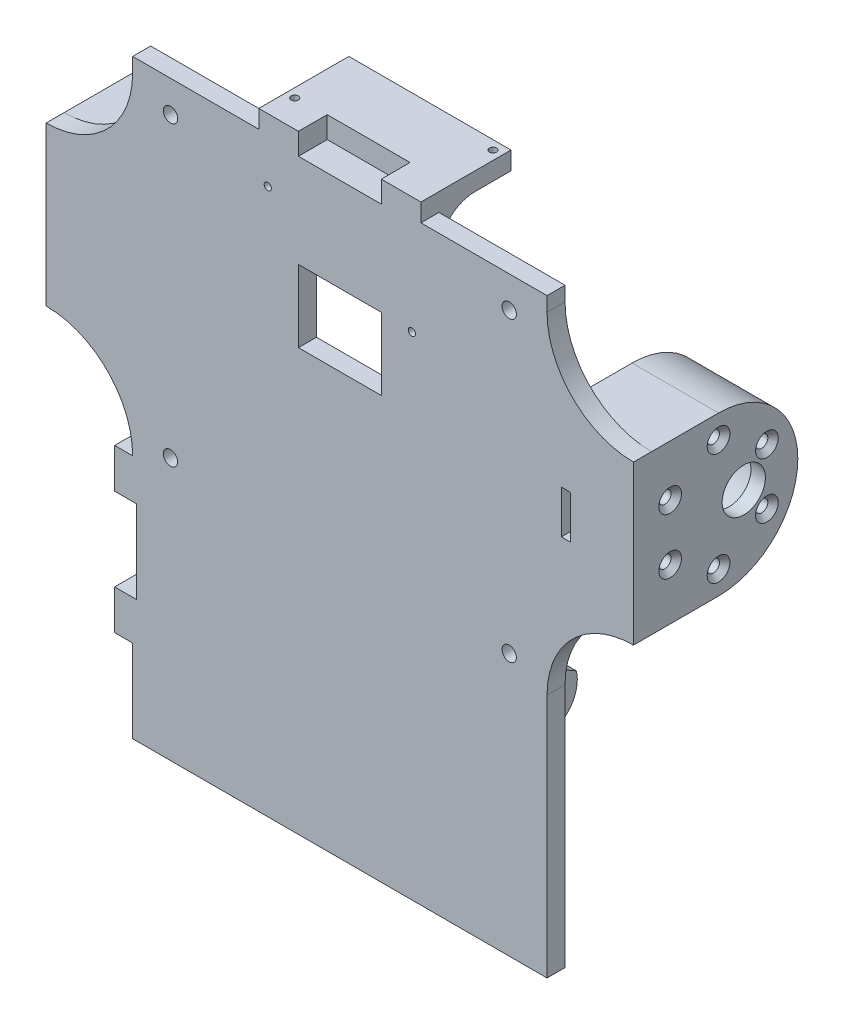
SolidWorks part; units mm, degrees
ref_plane "Front Plane" through (0, 0, 0) normal (0, 0, 1) x (1, 0, 0)
ref_plane "Top Plane" through (0, 0, 0) normal (0, 1, 0) x (1, 0, 0)
ref_plane "Right Plane" through (0, 0, 0) normal (1, 0, 0) x (0, 0, -1)
sketch "Sketch1" plane through (0, 0, 0) normal (0, 0, 1) x (1, 0, 0)
  line L0 (0, 0) -> (7, 5.25) construction
  line L1 (0, 0) -> (115, 0)
  line L2 (0, 0) -> (0, 100)
  line L3 (0, 100) -> (115, 100)
  line L4 (115, 0) -> (115, 100)
  line L5 (7, 94.75) -> (108, 94.75) construction
  line L6 (7, 94.75) -> (7, 5.25) construction
  line L7 (7, 5.25) -> (108, 5.25) construction
  line L8 (108, 94.75) -> (108, 5.25) construction
  line L9 (7, 94.75) -> (0, 100) construction
  line L10 (115, 100) -> (108, 94.75) construction
  line L11 (7, 94.75) -> (10.5, 91.25) construction
  line L12 (10.5, 91.25) -> (104.5, 91.25) construction
  line L13 (10.5, 91.25) -> (10.5, 8.75) construction
  line L14 (10.5, 8.75) -> (104.5, 8.75) construction
  line L15 (104.5, 91.25) -> (104.5, 8.75) construction
  line L16 (104.5, 91.25) -> (108, 94.75) construction
  line L17 (108, 5.25) -> (104.5, 8.75) construction
  line L18 (10.5, 8.75) -> (7, 5.25) construction
  circle A4 centre (10.5, 91.25) radius 2
  circle A5 centre (104.5, 91.25) radius 2
  circle A6 centre (104.5, 8.75) radius 2
  circle A7 centre (10.5, 8.75) radius 2
  dimension "D5" = 3.5
  dimension "D7" = 4
  dimension "D1" = 100
  dimension "D2" = 115
  dimension "D3" = 89.5
  dimension "D4" = 101
  dimension "D6" = 3.5
extrude "Boss-Extrude1" add sketch "Sketch1" along normal blind 5
sketch "Sketch2" plane through (0, 0, 5) normal (0, 0, 1) x (1, 0, 0)
  line L0 (115, 0) -> (115, 100) construction
  line L1 (0, 0) -> (115, 0)
  line L2 (0, 0) -> (0, -64)
  line L3 (0, -64) -> (115, -64)
  line L4 (115, 0) -> (115, -64)
  dimension "D1" = 64
extrude "Boss-Extrude2" add sketch "Sketch2" against normal up to surface (5 mm away) up to face at (106.5, 8.75, 0)
sketch "Sketch3" plane through (0, 0, 5) normal (0, 0, 1) x (1, 0, 0)
  line L0 (0, 100) -> (0, -64) construction
  line L1 (7, 2.75) -> (67, 2.75)
  line L2 (7, 2.75) -> (7, -59.25)
  line L3 (7, -59.25) -> (67, -59.25)
  line L4 (67, 2.75) -> (67, -59.25)
  circle A0 centre (10.5, 8.75) radius 2 construction
  dimension "D1" = 62
  dimension "D2" = 60
  dimension "D3" = 7
  dimension "D4" = 6
sketch "Sketch4" plane through (0, 100, 0) normal (0, 1, 0) x (1, 0, 0)
  line L0 (115, -5) -> (0, -5) construction
  line L2 (80, -5) -> (80, 20)
  line L3 (80, 20) -> (35, 20)
  line L4 (35, -5) -> (35, 20)
  line L5 (57.5, -5) -> (35, 20) construction
  line L6 (80, 20) -> (57.5, -5) construction
  line L7 (115, 0) -> (0, 0) construction
  line L8 (35, -5) -> (80, -5)
  line L9 (115, -5) -> (115, 0) construction
  point P0 (57.5, -5)
  dimension "D1" = 20
  dimension "D2" = 45
extrude "Boss-Extrude3" add sketch "Sketch4" along normal blind 5
sketch "Sketch5" plane through (0, 105, 0) normal (0, 1, 0) x (1, 0, 0)
  line L1 (0, 0) -> (115, 0) construction
  line L2 (35, 20) -> (35, -5) construction
  line L3 (80, -5) -> (80, 20) construction
  line L5 (80, 20) -> (35, 20) construction
  line L6 (35, 20) -> (46, -5) construction
  line L7 (46, 0) -> (69, 0) construction
  line L8 (46, 0) -> (46, -5) construction
  line L9 (46, -5) -> (69, -5) construction
  line L10 (69, 0) -> (69, -5) construction
  line L11 (69, -5) -> (80, 20) construction
  line L12 (35, -5) -> (80, -5) construction
  circle A0 centre (37.5, 2.5) radius 1
  circle A1 centre (77.5, 17.5) radius 1
  dimension "D5" = 2
  dimension "D1" = 2.5
  dimension "D2" = 2.5
  dimension "D3" = 2.5
  dimension "D4" = 2.5
  dimension "D6" = 5
  dimension "D7" = 23
extrude "Cut-Extrude2" cut sketch "Sketch5" against normal through all
fillet "Fillet1" radius 10 1 edges at (57.5, 100, 0)
sketch "Sketch6" plane through (0, 100, 0) normal (0, -1, 0) x (1, 0, 0)
  circle A0 centre (37.5, -2.5) radius 2.25
  dimension "D1" = 4.5
extrude "Cut-Extrude3" cut sketch "Sketch6" along normal through all
sketch "Sketch7" plane through (0, 105, 0) normal (0, 1, 0) x (1, 0, 0)
  line L1 (46, 3) -> (69, 3)
  line L2 (46, 3) -> (46, -5)
  line L3 (46, -5) -> (69, -5)
  line L4 (69, 3) -> (69, -5)
  dimension "D1" = 8
extrude "Cut-Extrude4" cut sketch "Sketch7" against normal blind 6
sketch "Sketch8" plane through (0, 0, 0) normal (0, 0, -1) x (-1, 0, 0)
  line L0 (-35, 90) -> (-35, 100) construction
  line L1 (-80, 90) -> (-35, 90) construction
  line L2 (-80, 90) -> (-80, 70) construction
  line L3 (-80, 70) -> (-35, 70) construction
  line L4 (-35, 90) -> (-35, 70) construction
  line L5 (-80, 70) -> (-69, 53) construction
  line L6 (-69, 73) -> (-46, 73)
  line L7 (-69, 73) -> (-69, 53)
  line L8 (-69, 53) -> (-46, 53)
  line L9 (-46, 73) -> (-46, 53)
  line L10 (-46, 53) -> (-35, 70) construction
  circle A0 centre (-37.5, 87.5) radius 1
  circle A1 centre (-77.5, 72.5) radius 1
  dimension "D2" = 2
  dimension "D3" = 2.5
  dimension "D5" = 2.5
  dimension "D1" = 20
  dimension "D4" = 2.5
  dimension "D6" = 2.5
  dimension "D7" = 23
  dimension "D8" = 20
  dimension "D9" = 3
extrude "Cut-Extrude5" cut sketch "Sketch8" against normal through all
ref_plane "Plane1" through (57.5, 0, 0) normal (-1, 0, 0) x (0, 0, 1)
sketch "Sketch9" plane through (115, 0, 0) normal (1, 0, 0) x (0, 0, -1)
  line L0 (0, 0) -> (0, 28) construction
  line L2 (0, 50) -> (18.6, 50) construction
  line L4 (18.6, 72) -> (0, 72)
  line L6 (18.6, 28) -> (0, 28)
  line L8 (-5, -64) -> (-5, 100) construction
  line L9 (0, 72) -> (-5, 72)
  line L11 (0, 28) -> (-5, 28)
  line L13 (-5, 72) -> (-5, 28)
  circle A0 centre (18.6, 50) radius 18.5
  arc A1 (18.6, 28) -> (18.6, 72) centre (18.6, 50) ccw
  dimension "D2" = 37
  dimension "D3" = 44
  dimension "D1" = 50
  dimension "D4" = 18.6
extrude "Boss-Extrude4" add sketch "Sketch9" along normal blind 20 separate body
sketch "Sketch10" plane through (135, 0, 0) normal (1, 0, 0) x (0, 0, -1)
  line L0 (18.6, 50) -> (34.1, 50) construction
  line L1 (32.0234, 57.75) -> (18.6, 50) construction
  line L2 (-5, 28) -> (18.6, 28) construction
  line L4 (18.6, 72) -> (-5, 72) construction
  line L5 (-5, 28) -> (18.6, 28)
  line L6 (-5, 72) -> (-5, 28)
  line L7 (18.6, 72) -> (-5, 72)
  circle A2 centre (18.6, 50) radius 18.5 construction
  circle A3 centre (18.6, 50) radius 18.5 construction
  circle A4 centre (25.6, 50) radius 6
  circle A5 centre (18.6, 50) radius 15.5 construction
  arc A6 (18.6, 28) -> (18.6, 72) centre (18.6, 50) ccw
  point P11 (32.0234, 57.75)
  point P17 (32.0234, 42.25)
  point P18 (18.6, 34.5)
  point P19 (5.1766, 42.25)
  point P20 (5.1766, 57.75)
  point P21 (18.6, 65.5)
  point P22 (18.6, 50)
  dimension "D1" = 12
  dimension "D3" = 31
  dimension "D2" = 7
  dimension "D4" = 30
  dimension "D5" = 6
extrude "Boss-Extrude5" add sketch "Sketch10" along normal blind 4
hole_wizard "CSK for M3 Flat Head Machine Screw1" positions "Sketch11" profile "Sketch12" countersink size "M3" standard "ANSI Metric" end condition through all
sketch "Sketch11" plane through (139, 0, 0) normal (1, 0, 0) x (0, 0, -1)
  point P0 (32.0234, 57.75)
  point P3 (18.6, 65.5)
  point P6 (5.1766, 57.75)
  point P9 (5.1766, 42.25)
  point P12 (18.6, 34.5)
  point P15 (32.0234, 42.25)
sketch "Sketch12" plane through (139, 57.75, -32.0234) normal (0, 1, 0) x (0, 0, -1)
  line L0 (0, 0) -> (0, 139)
  line L1 (0, 139) -> (1.7, 139)
  line L2 (1.7, 139) -> (1.7, 1.45)
  line L3 (1.7, 1.45) -> (3.15, 0)
  line L5 (3.15, 0) -> (0, 0)
  line L6 (-1.7, 1.45) -> (-3.15, 0) construction
  line L11 (0, -6.35) -> (0, 107.95) construction
  dimension "Thru Hole Dia." = 3.4
  dimension "Thru Hole Depth" = 139
  dimension "Near C'Sink Dia." = 6.3
  dimension "Near C'Sink Angle" = 90
mirror "Mirror10" about plane through (57.5, 0, 0) normal (-1, 0, 0) of "CSK for M3 Flat Head Machine Screw1", "Boss-Extrude5", "Boss-Extrude4"
sketch "Sketch15" plane through (0, 0, 0) normal (0, 0, -1) x (-1, 0, 0)
  line L0 (-139, 72) -> (-115, 72) construction
  line L1 (-115, -64) -> (-115, 100) construction
  line L2 (-139, 28) -> (-115, 28) construction
  line L3 (0, 28) -> (0, -64) construction
  line L4 (24, 28) -> (0, 28) construction
  line L5 (0, 100) -> (0, 72) construction
  line L6 (24, 72) -> (0, 72) construction
  line L7 (24, 72) -> (0, 72)
  line L8 (0, 72) -> (0, 96)
  line L9 (24, 28) -> (0, 28)
  line L10 (0, 28) -> (0, 4)
  line L11 (-115, 4) -> (-115, 28)
  line L12 (-115, 28) -> (-115, 72) construction
  line L13 (-115, 28) -> (-139, 28)
  line L14 (-115, 96) -> (-115, 72)
  line L15 (-115, 72) -> (-139, 72)
  arc A0 (-139, 72) -> (-115, 96) centre (-139, 96) ccw
  arc A1 (-115, 4) -> (-139, 28) centre (-139, 4) ccw
  arc A2 (0, 96) -> (24, 72) centre (24, 96) ccw
  arc A3 (24, 28) -> (0, 4) centre (24, 4) ccw
extrude "Boss-Extrude6" add sketch "Sketch15" against normal up to surface (5 mm away) up to face at (36.5, 87.5, 5)
ref_plane "Plane2" through (50.4, 0, 0) normal (-1, 0, 0) x (0, 0, 1)
sketch "Sketch16" plane through (50.4, 0, 0) normal (-1, 0, 0) x (0, 0, 1)
  line L0 (0, -9.5117) -> (-32.8318, -28.4672)
  line L1 (0, 4) -> (0, -64) construction
  line L2 (0, -9.5117) -> (0, -24.5117)
  line L3 (0, -24.5117) -> (-28.1738, -40.7779)
  line L4 (0, -17.0117) -> (-34.35, -36.8437) construction
  line L5 (-32.8318, -28.4672) -> (-43.5456, -34.6528)
  line L6 (-28.1738, -40.7779) -> (-37.0504, -45.9028)
  circle A0 centre (-34.35, -36.8437) radius 3.5
  arc A2 (-43.5456, -34.6528) -> (-37.0504, -45.9028) centre (-34.35, -36.8437) ccw
  dimension "D4" = 7
  dimension "D1" = 15
  dimension "D2" = 120
  dimension "D3" = 34.35
extrude "Boss-Extrude7" add sketch "Sketch16" along normal blind 10
mirror "Mirror11" about plane through (57.5, 0, 0) normal (-1, 0, 0) of "Boss-Extrude7"
fillet "Fillet3" radius 20 2 edges at (40.4, -17.0117, 0) (74.6, -17.0117, 0)
fillet "Fillet4" radius 5 4 edges at (35.4, -24.5117, 0) (79.6, -24.5117, 0) (35.4, -9.5117, 0) (79.6, -9.5117, 0)
sketch "Sketch19" plane through (0, 0, 0) normal (-1, 0, 0) x (0, 0, 1)
  line L0 (5, 4) -> (-20, 4)
  line L1 (-20, 4) -> (-20, -41)
  line L2 (5, -41) -> (-20, -41)
  line L3 (5.2881, -18.5) -> (-20, -41) construction
  line L4 (-20, 4) -> (5.2881, -18.5) construction
  line L5 (5, -41) -> (5, 4)
  line L8 (5, 4) -> (0, 4) construction
  line L9 (5, 4) -> (5, -64) construction
  point P0 (5.2881, -18.5)
  dimension "D1" = 45
  dimension "D2" = 25
extrude "Boss-Extrude9" add sketch "Sketch19" along normal blind 5
sketch "Sketch20" plane through (-5, 0, 0) normal (-1, 0, 0) x (0, 0, 1)
  line L0 (-20, 4) -> (-20, -41) construction
  line L1 (5, 4) -> (-20, 4) construction
  line L2 (0, -41) -> (0, -64) construction
  line L3 (-20, -41) -> (5, -41) construction
  circle A0 centre (-17.5, 1.5) radius 1
  circle A1 centre (-2.5, -38.5) radius 1
  dimension "D2" = 2.5
  dimension "D3" = 2
  dimension "D1" = 2.5
  dimension "D4" = 2.5
  dimension "D5" = 2.5
extrude "Cut-Extrude6" cut sketch "Sketch20" against normal up to surface (5 mm away) up to face at (0, -18.5, -10)
fillet "Fillet5" radius 10 1 edges at (0, -18.5, 0)
sketch "Sketch21" plane through (-5, 0, 0) normal (-1, 0, 0) x (0, 0, 1)
  line L0 (5, -41) -> (5, 4) construction
  line L1 (5, -7) -> (-3, -7)
  line L2 (5, -7) -> (5, -30)
  line L3 (5, -30) -> (-3, -30)
  line L4 (-3, -7) -> (-3, -30)
  line L5 (5, 4) -> (-3, -7) construction
  line L6 (5, -41) -> (-3, -30) construction
  dimension "D1" = 8
  dimension "D2" = 23
extrude "Cut-Extrude7" cut sketch "Sketch21" against normal blind 6
sketch "Sketch22" plane through (0, 0, 0) normal (1, 0, 0) x (0, 0, -1)
  circle A0 centre (2.5, -38.5) radius 2.25
  dimension "D1" = 4.5
extrude "Cut-Extrude8" cut sketch "Sketch22" along normal blind 15
sketch "Sketch23" plane through (0, 0, 5) normal (0, 0, 1) x (1, 0, 0)
  line L0 (139, 72) -> (146.9997, 56) construction
  line L1 (116.9997, 44) -> (116.9997, 56) construction
  line L2 (116.9997, 44) -> (146.9997, 44) construction
  line L3 (146.9997, 44) -> (146.9997, 56) construction
  line L4 (116.9997, 56) -> (146.9997, 56) construction
  line L5 (139, 28) -> (146.9997, 44) construction
  line L7 (139, 72) -> (139, 28) construction
  line L8 (121.4997, 44) -> (121.4997, 55.9635)
  line L9 (121.4997, 44) -> (119, 44.0365)
  line L10 (119, 44.0365) -> (119, 56)
  line L11 (121.4997, 55.9635) -> (119, 56)
  dimension "D1" = 30
  dimension "D2" = 12
  dimension "D3" = 20
  dimension "D4" = 2.5
  dimension "D5" = 4.5
extrude "Cut-Extrude10" cut sketch "Sketch23" against normal blind 12
